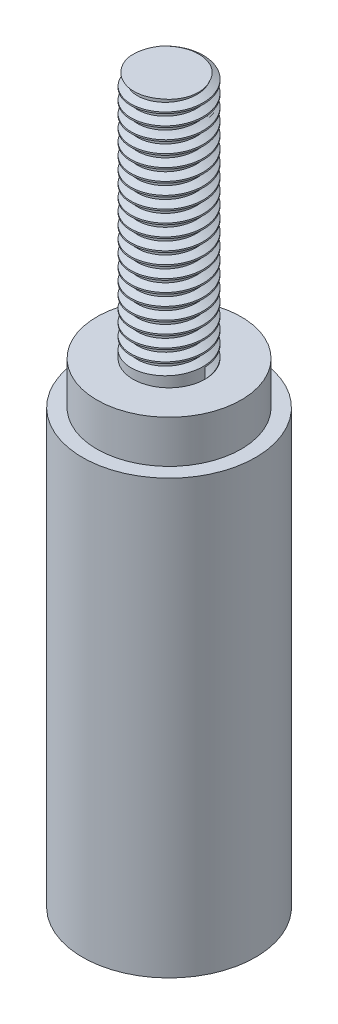
SolidWorks part; units mm, degrees
ref_plane "Front" through (0, 0, 0) normal (0, 0, 1) x (1, 0, 0)
ref_plane "Top" through (0, 0, 0) normal (0, 1, 0) x (1, 0, 0)
ref_plane "Right" through (0, 0, 0) normal (1, 0, 0) x (0, 0, -1)
sketch "Sketch1" plane through (0, 0, 0) normal (0, 1, 0) x (1, 0, 0)
  circle A0 centre (0, 0) radius 15.24
  dimension "D1" = 30.48
extrude "Boss-Extrude1" add sketch "Sketch1" along normal blind 76.2
sketch "Sketch2" plane through (0, 76.2, 0) normal (0, 1, 0) x (1, 0, 0)
  circle A0 centre (0, 0) radius 12.7
  dimension "D1" = 25.4
extrude "Boss-Extrude2" add sketch "Sketch2" along normal blind 7.493
sketch "Sketch3" plane through (0, 83.693, 0) normal (0, 1, 0) x (1, 0, 0)
  circle A0 centre (0, 0) radius 6.35
  dimension "D1" = 12.7
extrude "Boss-Extrude3" add sketch "Sketch3" along normal blind 43.18
thread "Thread1" pitch 2.1167 profile "Thread Profile1" start angle 0, offset 0, length 121.92, pitch 2.1167, diameter 12.7
ref_plane "Plane1" through (6.35, 83.693, 0) normal (0, 0, 1) x (1, 0, 0)
sketch "Thread Profile1" plane through (6.35, 83.693, 0) normal (0, 0, 1) x (1, 0, 0)
  line L0 (0, 0) -> (0, 2.1167) construction
  line L11 (0, 0) -> (0, 1.8521)
  line L12 (0, 1.8521) -> (-1.1457, 1.1906)
  line L13 (-1.1457, 1.1906) -> (-1.1457, 0.6615)
  line L15 (-1.1457, 0.6615) -> (0, 0)
  line L17 (-1.1457, 0.926) -> (0, 0.926) construction
  point P2 (0, 0)
  dimension "Pitch" = 2.1167
  dimension "Profile_Angle" = 60
  dimension "Profile_Land" = 0.5292
  dimension "Profile_Height" = 1.1457
